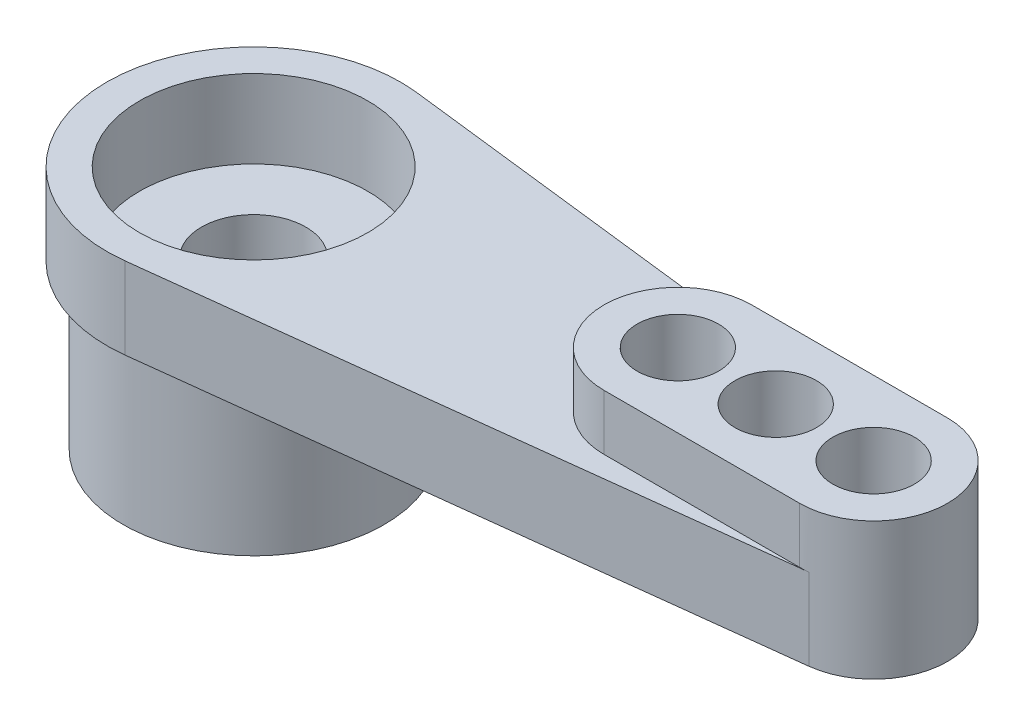
SolidWorks part; units mm, degrees
ref_plane "Plan de face" through (0, 0, 0) normal (0, 0, 1) x (1, 0, 0)
ref_plane "Plan de dessus" through (0, 0, 0) normal (0, 1, 0) x (1, 0, 0)
ref_plane "Plan de droite" through (0, 0, 0) normal (1, 0, 0) x (0, 0, -1)
sketch "Esquisse1" plane through (0, 0, 0) normal (0, 1, 0) x (1, 0, 0)
  line L0 (0, 0) -> (19, 0) construction
  line L1 (0.5292, 4.4688) -> (19.2664, 2.25)
  line L2 (0.5292, -4.4688) -> (19.2664, -2.25)
  line L3 (0, 4.5) -> (0, -4.5) construction
  arc A0 (0.5292, 4.4688) -> (0.5292, -4.4688) centre (0, 0) ccw
  arc A1 (19.2664, 2.25) -> (19.2664, -2.25) centre (19, 0) cw
  point P6 (0, 0)
  dimension "D1" = 19
  dimension "D2" = 9
  dimension "D3" = 4.5
extrude "Boss.-Extru.1" add sketch "Esquisse1" along normal blind 2.5
sketch "Esquisse2" plane through (0, 0, 0) normal (0, -1, 0) x (1, 0, 0)
  circle A0 centre (0, 0) radius 4
  dimension "D1" = 8
extrude "Boss.-Extru.2" add sketch "Esquisse2" along normal blind 5
sketch "Esquisse3" plane through (0, -5, 0) normal (0, -1, 0) x (1, 0, 0)
  circle A0 centre (0, 0) radius 2.7
  dimension "D1" = 5.4
extrude "Enlèv. mat.-Extru.1" cut sketch "Esquisse3" against normal blind 2.4
hole_wizard "Chambrage pour vis à tête ronde bombée M31" positions "Esquisse4" profile "Esquisse5" counterbore size "M3" standard "DIN" end condition through all
sketch "Esquisse4" plane through (0, 2.5, 0) normal (0, 1, 0) x (1, 0, 0)
  point P0 (0, 0)
sketch "Esquisse5" plane through (0, 2.5, 0) normal (1, 0, 0) x (0, 0, 1)
  line L0 (0, 0) -> (0, 7.5)
  line L1 (0, 7.5) -> (1.6, 7.5)
  line L3 (1.6, 7.5) -> (1.6, 2.4)
  line L4 (1.6, 2.4) -> (3.5, 2.4)
  line L5 (3.5, 2.4) -> (3.5, 0)
  line L7 (3.5, 0) -> (0, 0)
  line L11 (0, -6.35) -> (0, 107.95) construction
  dimension "Diamètre du perçage jusqu'au prochain" = 3.2
  dimension "Profondeur du perçage jusqu'au prochain" = 7.5
  dimension "Diamètre du chambrage" = 7
  dimension "Profondeur du chambrage" = 2.4
sketch "Esquisse6" plane through (0, 2.5, 0) normal (0, 1, 0) x (1, 0, 0)
  line L0 (19, 0) -> (13, 0) construction
  line L1 (19, -2.2657) -> (13, -2.2657)
  line L2 (19, 2.2657) -> (13, 2.2657)
  arc A0 (19, -2.2657) -> (19, 2.2657) centre (19, 0) ccw
  arc A1 (13, 2.2657) -> (13, -2.2657) centre (13, 0) ccw
  arc A2 (19.2664, -2.25) -> (19.2664, 2.25) centre (19, 0) ccw construction
  point P2 (16, 0)
  dimension "D1" = 13
extrude "Boss.-Extru.3" add sketch "Esquisse6" along normal blind 1.7
hole_wizard "Diamètre du perçage Ø2.5 (2.5)1" positions "Esquisse9" profile "Esquisse10" hole size "Ø2.5" standard "DIN" end condition through all
sketch "Esquisse9" plane through (0, 4.2, 0) normal (0, 1, 0) x (1, 0, 0)
  point P0 (13, 0)
  point P2 (16, 0)
  point P4 (19, 0)
  dimension "D1" = 13
  dimension "D2" = 16
  dimension "D3" = 19
sketch "Esquisse10" plane through (13, 4.2, 0) normal (1, 0, 0) x (0, 0, 1)
  line L0 (0, 0) -> (0, 9.2)
  line L1 (0, 9.2) -> (1.25, 9.2)
  line L2 (1.25, 9.2) -> (1.25, 0)
  line L5 (1.25, 0) -> (0, 0)
  line L11 (0, -6.35) -> (0, 107.95) construction
  dimension "Diamètre du perçage jusqu'au prochain" = 2.5
  dimension "Profondeur du perçage jusqu'au prochain" = 9.2
ref_axis "Axe1" through (13, 0, 0) along (0, 1, 0)
